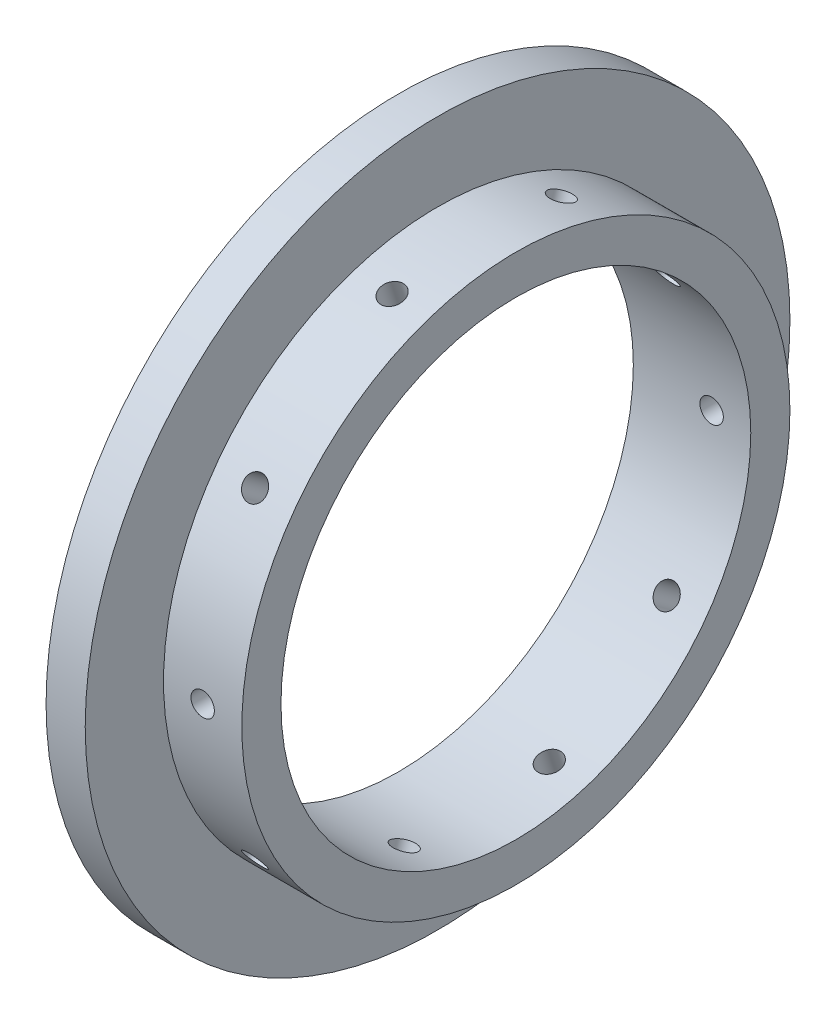
SolidWorks part; units mm, degrees
material "Alloy Steel"
ref_plane "Front Plane" through (0, 0, 0) normal (0, 0, 1) x (1, 0, 0)
ref_plane "Top Plane" through (0, 0, 0) normal (0, 1, 0) x (1, 0, 0)
ref_plane "Right Plane" through (0, 0, 0) normal (1, 0, 0) x (0, 0, -1)
sketch "Sketch1" plane through (0, 0, 0) normal (1, 0, 0) x (0, 0, -1)
  circle A0 centre (0, 0) radius 38.1
  circle A1 centre (0, 0) radius 57.15
  dimension "D1" = 76.2
  dimension "D2" = 114.3
extrude "Boss-Extrude1" add sketch "Sketch1" along normal blind 6.35
sketch "Sketch2" plane through (6.35, 0, 0) normal (1, 0, 0) x (0, 0, -1)
  circle A0 centre (0, 0) radius 44.45
  circle A1 centre (0, 0) radius 38.1
  dimension "D1" = 88.9
  dimension "D2" = 76.2
extrude "Boss-Extrude2" add sketch "Sketch2" along normal blind 12.7
sketch "Sketch3" plane through (0, 0, 0) normal (0, 1, 0) x (1, 0, 0)
  line L0 (0, 0) -> (88.5884, 0) construction
  line L1 (-13.97, 0) -> (13.97, 0) construction
  line L2 (0, 0) -> (0, 82.8947) construction
ref_plane "Plane1" through (0, 0, -44.45) normal (0, 0, -1) x (-1, 0, 0)
sketch "Sketch4" plane through (0, 0, -44.45) normal (0, 0, -1) x (-1, 0, 0)
  line L0 (0, 0) -> (-88.5884, 0) construction
  line L2 (-6.35, 44.45) -> (-6.35, -44.45) construction
  circle A0 centre (-12.7, 0) radius 1.8986
  dimension "D2" = 3.7973
  dimension "D1" = 6.35
extrude "Cut-Extrude1" cut sketch "Sketch4" against normal blind 7.62
pattern_circular "CirPattern1" count 10 over 360 about axis through (0, 0, 0) along (1, 0, 0) of "Cut-Extrude1"
